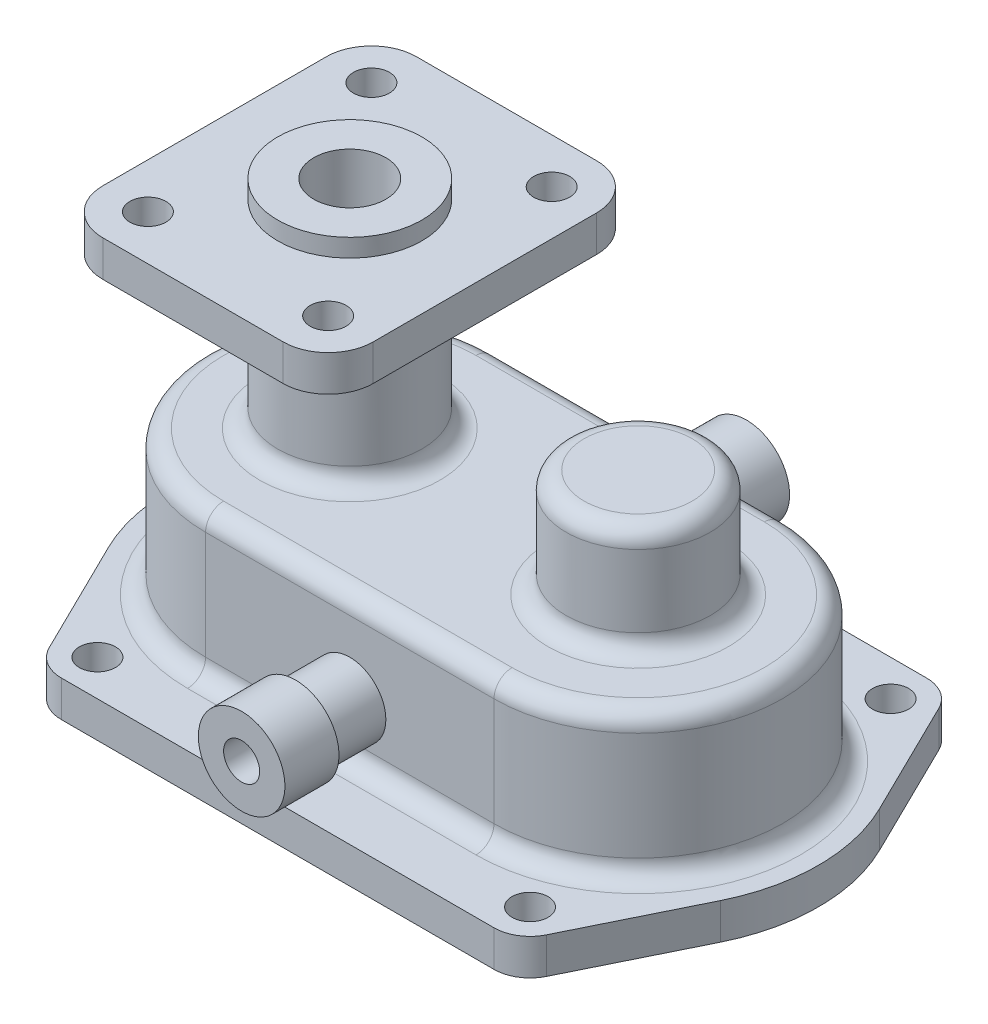
SolidWorks part; units mm, degrees
ref_plane "Front Plane" through (0, 0, 0) normal (0, 0, 1) x (1, 0, 0)
ref_plane "Top Plane" through (0, 0, 0) normal (0, 1, 0) x (1, 0, 0)
ref_plane "Right Plane" through (0, 0, 0) normal (1, 0, 0) x (0, 0, -1)
sketch "Sketch1" plane through (0, 0, 0) normal (0, 1, 0) x (1, 0, 0)
  line L0 (-40, 0) -> (40, 0) construction
  line L1 (-60, -60) -> (60, -60)
  line L3 (-60, 60) -> (60, 60)
  line L5 (-70, -55.7885) -> (70, 55.7885) construction
  line L6 (-70, 55.7885) -> (70, -55.7885) construction
  line L7 (-68.9751, 54.41) -> (-84.8754, 22.0498)
  line L8 (-68.9751, -54.41) -> (-84.8754, -22.0498)
  line L9 (0, -19.6369) -> (0, 19.6369) construction
  line L10 (68.9751, -54.41) -> (84.8754, -22.0498)
  line L11 (68.9751, 54.41) -> (84.8754, 22.0498)
  arc A0 (-68.9751, 54.41) -> (-60, 60) centre (-60, 50) cw
  arc A1 (-60, -60) -> (-68.9751, -54.41) centre (-60, -50) cw
  arc A2 (60, -60) -> (68.9751, -54.41) centre (60, -50) ccw
  arc A3 (60, 60) -> (68.9751, 54.41) centre (60, 50) cw
  arc A4 (84.8754, -22.0498) -> (84.8754, 22.0498) centre (40, 0) ccw
  arc A5 (-84.8754, 22.0498) -> (-84.8754, -22.0498) centre (-40, 0) ccw
  circle A6 centre (-60, 50) radius 5
  circle A7 centre (-60, -50) radius 5
  circle A8 centre (60, -50) radius 5
  circle A9 centre (60, 50) radius 5
  point P0 (0, 0)
  point P21 (0, 0)
  point P30 (0, 0)
  dimension "D1" = 10
  dimension "D3" = 100
  dimension "D6" = 10
  dimension "D2" = 80
  dimension "D4" = 120
  dimension "D5" = 100
extrude "Boss-Extrude1" add sketch "Sketch1" along normal blind 10
sketch "Sketch2" plane through (0, 10, 0) normal (0, 1, 0) x (1, 0, 0)
  line L0 (-40, 0) -> (40, 0) construction
  line L1 (-40, 40) -> (40, 40)
  line L2 (-40, -40) -> (40, -40)
  arc A0 (-40, 40) -> (-40, -40) centre (-40, 0) ccw
  arc A1 (40, -40) -> (40, 40) centre (40, 0) ccw
  point P4 (0, 0)
  point P9 (0, 0)
  dimension "D1" = 40
extrude "Boss-Extrude2" add sketch "Sketch2" along normal blind 40
shell "Shell2" thickness 10 removed face at (-60, 0, -45)
sketch "Sketch3" plane through (0, 40, 0) normal (0, -1, 0) x (1, 0, 0)
  circle A1 centre (40, 0) radius 20
  dimension "D1" = 40
extrude "Boss-Extrude3" add sketch "Sketch3" against normal blind 30 from offset 10 offset against normal yes
sketch "Sketch4" plane through (0, 40, 0) normal (0, -1, 0) x (1, 0, 0)
  circle A0 centre (40, 0) radius 10
  dimension "D1" = 20
extrude "Cut-Extrude1" cut sketch "Sketch4" against normal blind 30
sketch "Sketch5" plane through (0, 40, 0) normal (0, -1, 0) x (1, 0, 0)
  circle A0 centre (-40, 0) radius 20
  circle A1 centre (-40, 0) radius 10
  dimension "D1" = 40
  dimension "D2" = 20
extrude "Boss-Extrude4" add sketch "Sketch5" against normal blind 70
extrude "Cut-Extrude3" cut sketch "Sketch5<3>" against normal blind 10 contours A1
sketch "Sketch5<3>" plane through (0, 40, 0) normal (0, -1, 0) x (1, 0, 0) same geometry as "Sketch5"
sketch "Sketch7" plane through (0, 110, 0) normal (0, 1, 0) x (1, 0, 0)
  line L1 (-65, -43.5) -> (-15, -43.5)
  line L2 (-77.5, -31) -> (-77.5, 31)
  line L3 (-65, 43.5) -> (-15, 43.5)
  line L4 (-2.5, -31) -> (-2.5, 31)
  line L5 (-77.5, -43.5) -> (-2.5, 43.5) construction
  line L6 (-77.5, 43.5) -> (-2.5, -43.5) construction
  arc A0 (-77.5, 31) -> (-65, 43.5) centre (-65, 31) cw
  arc A1 (-15, -43.5) -> (-2.5, -31) centre (-15, -31) ccw
  arc A2 (-15, 43.5) -> (-2.5, 31) centre (-15, 31) cw
  arc A3 (-65, -43.5) -> (-77.5, -31) centre (-65, -31) cw
  circle A4 centre (-40, 0) radius 20
  circle A5 centre (-15, 31) radius 5
  circle A6 centre (-65, 31) radius 5
  circle A7 centre (-15, -31) radius 5
  circle A8 centre (-65, -31) radius 5
  point P0 (-40, 0)
  point P24 (0, 0)
  point P25 (0, 0)
  dimension "D3" = 12.5
  dimension "D4" = 40
  dimension "D5" = 10
  dimension "D1" = 75
  dimension "D2" = 87
extrude "Boss-Extrude6" add sketch "Sketch7" along normal blind 10 from offset 15 offset against normal yes
sketch "Sketch10" plane through (0, 0, 0) normal (0, 0, 1) x (1, 0, 0)
  line L0 (-40, 50) -> (-40, 10) construction
  circle A0 centre (0, 25) radius 10
  circle A1 centre (0, 25) radius 5
  dimension "D1" = 20
  dimension "D2" = 10
  dimension "D3" = 25
  dimension "D4" = 40
extrude "Boss-Extrude7" add sketch "Sketch10" along normal mid plane 140
sketch "Sketch11" plane through (0, 0, 0) normal (0, -1, 0) x (1, 0, 0)
  line L0 (-40, 0) -> (40, 0) construction
  line L1 (-40, 30) -> (40, 30)
  line L2 (-40, -30) -> (40, -30)
  arc A0 (-40, 30) -> (-40, -30) centre (-40, 0) ccw
  arc A1 (40, -30) -> (40, 30) centre (40, 0) ccw
  point P4 (0, 0)
  dimension "D1" = 30
extrude "Cut-Extrude4" cut sketch "Sketch11" against normal up to surface (40 mm away) up to face at (-40, 40, -10)
sketch "Sketch12" plane through (0, 0, -40) normal (0, 0, -1) x (-1, 0, 0)
  circle A0 centre (0, 25) radius 5
  circle A1 centre (0, 25) radius 10 construction
  dimension "D1" = 10
extrude "Cut-Extrude5" cut sketch "Sketch12" against normal mid plane 285
sketch "Sketch13" plane through (0, 0, -70) normal (0, 0, -1) x (-1, 0, 0)
  circle A0 centre (0, 25) radius 12
  circle A1 centre (0, 25) radius 10
  dimension "D1" = 24
extrude "Boss-Extrude8" add sketch "Sketch13" against normal blind 15
mirror "Mirror1" about plane through (0, 0, 0) normal (0, 0, 1) of "Boss-Extrude8"
fillet "Fillet1" radius 5 16 edges at (-70, 40, 0) (0, 40, -30) (70, 40, 0) (-80, 50, 0) (0, 50, -40) (80, 50, 0) (-80, 10, 0) (0, 10, -40) (80, 10, 0) (-40, 95, -20) (-40, 50, 20) (0, 40, 30) (40, 80, -20) (40, 50, 20) (0, 50, 40) (0, 10, 40)
